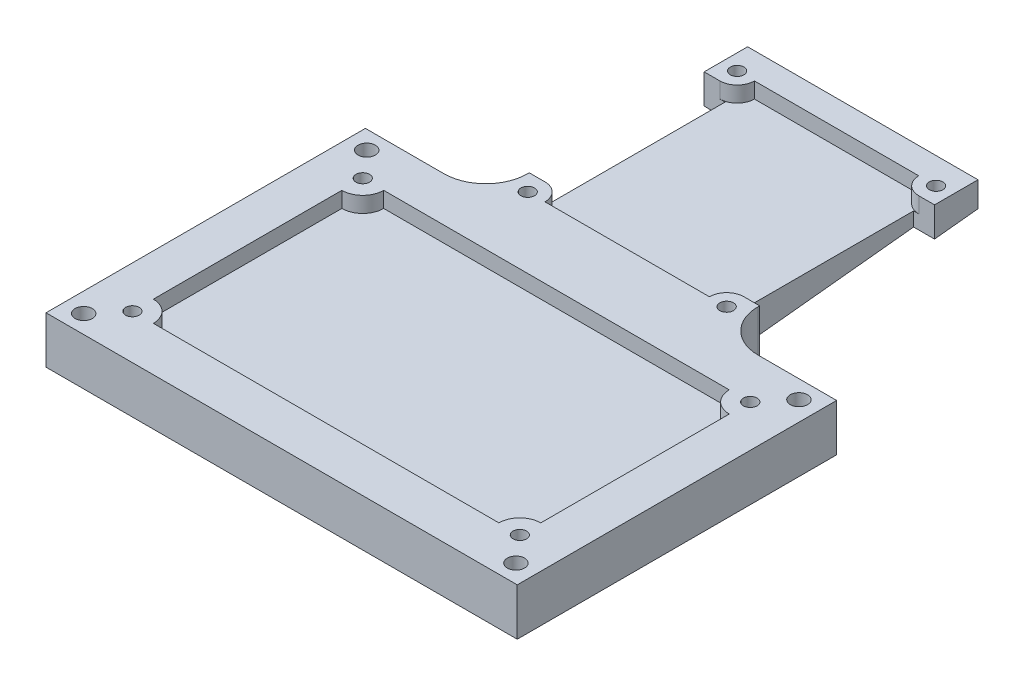
SolidWorks part; units mm, degrees
ref_plane "Front Plane" through (0, 0, 0) normal (0, 0, 1) x (1, 0, 0)
ref_plane "Top Plane" through (0, 0, 0) normal (0, 1, 0) x (1, 0, 0)
ref_plane "Right Plane" through (0, 0, 0) normal (1, 0, 0) x (0, 0, -1)
sketch "Sketch1" plane through (0, 0, 0) normal (0, 1, 0) x (1, 0, 0)
  line L0 (0, 0) -> (90, 0)
  line L1 (90, 0) -> (90, 61)
  line L2 (90, 61) -> (75, 61)
  line L3 (0, 61) -> (0, 0)
  line L4 (86.275, 3.475) -> (86.275, 57.525) construction
  line L5 (86.275, 57.525) -> (3.725, 57.525) construction
  line L6 (15, 61) -> (0, 61)
  line L8 (23, 69) -> (23, 111)
  line L9 (23, 111) -> (67, 111)
  line L10 (67, 69) -> (67, 111)
  circle A0 centre (3.725, 57.525) radius 1.65
  circle A1 centre (86.275, 57.525) radius 1.65
  circle A2 centre (86.275, 3.475) radius 1.65
  circle A3 centre (3.725, 3.475) radius 1.65
  arc A4 (15, 61) -> (23, 69) centre (15, 69) ccw
  arc A5 (75, 61) -> (67, 69) centre (75, 69) cw
  point P12 (86.275, 30.5)
  point P13 (90, 30.5)
  point P14 (45, 57.525)
  point P21 (45, 111)
  point P23 (23, 61)
  point P26 (45, 0)
  dimension "D5" = 3.3
  dimension "D6" = 3.3
  dimension "D7" = 3.3
  dimension "D8" = 44
  dimension "D10" = 8
  dimension "D11" = 8
  dimension "D1" = 61
  dimension "D2" = 90
  dimension "D3" = 82.55
  dimension "D4" = 54.05
  dimension "D9" = 50
extrude "Boss-Extrude1" add sketch "Sketch1" along normal blind 9
chamfer "Chamfer1" distance 40 angle 6 1 edges at (45, 0, -111) first distance on face at (86.275, 0, -1.825)
sketch "Sketch2" plane through (0, 9, 0) normal (0, 1, 0) x (1, 0, 0)
  line L0 (0, 0) -> (90, 0) construction
  line L1 (8, 52.5) -> (82, 52.5) construction
  line L2 (8, 52.5) -> (8, 8.5) construction
  line L3 (8, 8.5) -> (82, 8.5) construction
  line L4 (82, 52.5) -> (82, 8.5) construction
  line L5 (0, 61) -> (0, 0) construction
  circle A0 centre (8, 52.5) radius 1.3
  circle A1 centre (8, 8.5) radius 1.3
  circle A2 centre (82, 52.5) radius 1.3
  circle A3 centre (82, 8.5) radius 1.3
  point P10 (45, 0)
  point P11 (45, 8.5)
  point P14 (0, 30.5)
  point P15 (8, 30.5)
  dimension "D3" = 2.6
  dimension "D4" = 2.6
  dimension "D5" = 2.6
  dimension "D6" = 2.6
  dimension "D1" = 74
  dimension "D2" = 44
extrude "Cut-Extrude1" cut sketch "Sketch2" against normal through all
sketch "Sketch3" plane through (0, 9, 0) normal (0, 1, 0) x (1, 0, 0)
  line L0 (67, 111) -> (23, 111) construction
  line L1 (26, 106) -> (64, 106) construction
  line L2 (26, 106) -> (26, 66) construction
  line L3 (26, 66) -> (64, 66) construction
  line L4 (64, 106) -> (64, 66) construction
  line L5 (23, 111) -> (23, 69) construction
  circle A0 centre (26, 106) radius 1.3
  circle A1 centre (64, 106) radius 1.3
  circle A2 centre (26, 66) radius 1.3
  circle A3 centre (64, 66) radius 1.3
  dimension "D3" = 5
  dimension "D1" = 40
  dimension "D2" = 38
  dimension "D4" = 3
extrude "Cut-Extrude2" cut sketch "Sketch3" against normal through all
sketch "Sketch4" plane through (0, 9, 0) normal (0, 1, 0) x (1, 0, 0)
  line L1 (12, 52.5) -> (78, 52.5)
  line L2 (8, 48.5) -> (8, 12.5)
  line L3 (12, 8.5) -> (78, 8.5)
  line L4 (82, 48.5) -> (82, 12.5)
  arc A0 (8, 48.5) -> (12, 52.5) centre (8, 52.5) ccw
  arc A1 (78, 52.5) -> (82, 48.5) centre (82, 52.5) ccw
  arc A2 (82, 12.5) -> (78, 8.5) centre (82, 8.5) ccw
  arc A3 (12, 8.5) -> (8, 12.5) centre (8, 8.5) ccw
extrude "Cut-Extrude3" cut sketch "Sketch4" against normal blind 3
sketch "Sketch5" plane through (0, 9, 0) normal (0, 1, 0) x (1, 0, 0)
  line L0 (29.3, 106) -> (60.7, 106)
  line L5 (45, 106) -> (45, 71.9475) construction
  line L6 (20.5, 86) -> (57.0983, 86) construction
  line L7 (26, 102.7) -> (26, 69.3)
  line L8 (64, 102.7) -> (64, 69.3)
  line L9 (29.3, 66) -> (60.7, 66)
  circle A4 centre (26, 106) radius 1.3 construction
  arc A5 (26, 102.7) -> (29.3, 106) centre (26, 106) ccw
  circle A6 centre (26, 66) radius 1.3 construction
  circle A7 centre (64, 106) radius 1.3 construction
  arc A8 (26, 69.3) -> (29.3, 66) centre (26, 66) cw
  arc A9 (60.7, 66) -> (64, 69.3) centre (64, 66) cw
  arc A10 (64, 102.7) -> (60.7, 106) centre (64, 106) cw
  point P24 (26, 86)
  point P25 (45, 106)
  dimension "D1" = 3.3
  dimension "D2" = 3.3
  dimension "D3" = 3.3
  dimension "D4" = 3.3
extrude "Cut-Extrude4" cut sketch "Sketch5" against normal blind 3
sketch "Sketch6" plane through (0, 9, 0) normal (0, 1, 0) x (1, 0, 0)
  line L0 (23, 111) -> (23, 69) construction
  line L1 (27, 102.7) -> (23, 102.7)
  line L2 (27, 102.7) -> (27, 69.3)
  line L3 (27, 69.3) -> (23, 69.3)
  line L4 (23, 102.7) -> (23, 69.3)
  line L5 (45, 106) -> (45, 66) construction
  line L6 (60.7, 106) -> (29.3, 106) construction
  line L7 (29.3, 66) -> (60.7, 66) construction
  line L8 (63, 69.3) -> (67, 69.3)
  line L9 (67, 102.7) -> (67, 69.3)
  line L10 (63, 102.7) -> (67, 102.7)
  line L11 (63, 102.7) -> (63, 69.3)
  dimension "D1" = 4
extrude "Cut-Extrude5" cut sketch "Sketch6" against normal through all
equation "\"D4@Sketch2\"=\"D3@Sketch2\""
equation "\"D5@Sketch2\"=\"D3@Sketch2\""
equation "\"D6@Sketch2\"=\"D3@Sketch2\""
